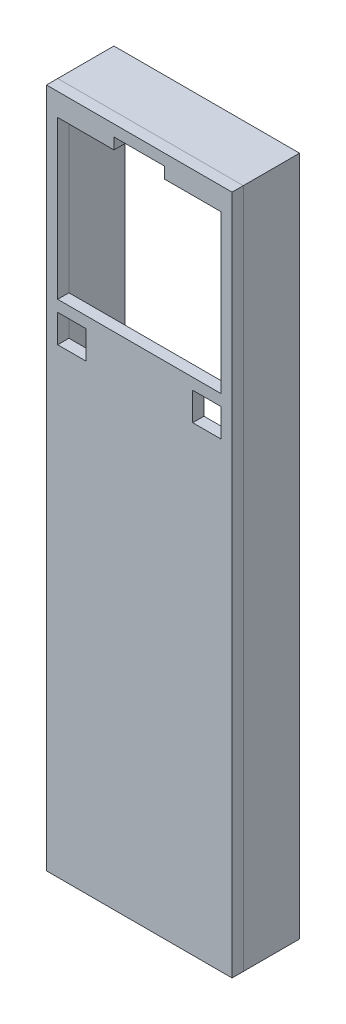
SolidWorks part; units mm, degrees
ref_plane "Plano frontal" through (0, 0, 0) normal (0, 0, 1) x (1, 0, 0)
ref_plane "Plano superior" through (0, 0, 0) normal (0, 1, 0) x (1, 0, 0)
ref_plane "Plano direito" through (0, 0, 0) normal (1, 0, 0) x (0, 0, -1)
sketch "Esboço1" plane through (0, 0, 0) normal (0, 0, 1) x (1, 0, 0)
  line L0 (0, 0) -> (0, 87)
  line L1 (0, 115) -> (29, 115)
  line L2 (29, 115) -> (29, 87)
  line L3 (29, 0) -> (0, 0)
  line L4 (0, 0) -> (0, 1.5)
  line L5 (0, 1.5) -> (1.5, 1.5)
  line L6 (14.5, 0) -> (14.5, 6.4035)
  line L7 (-2, -2) -> (-2, 119)
  line L8 (-2, 117) -> (31, 117)
  line L9 (31, 119) -> (31, -2)
  line L10 (31, -2) -> (-2, -2)
  line L11 (-2, 85) -> (24, 85)
  line L12 (0, 80) -> (5, 80)
  line L13 (0, 85) -> (5, 85)
  line L14 (5, 85) -> (5, 80)
  line L15 (0, 87) -> (24, 87)
  line L16 (24, 80) -> (24, 85)
  line L17 (24, 85) -> (31, 85)
  line L18 (24, 80) -> (29, 80)
  line L19 (0, 85) -> (29, 85) construction
  line L20 (24, 87) -> (29, 87)
  line L21 (0, 80) -> (29, 80) construction
  line L22 (0, 115) -> (10, 115)
  line L23 (10, 115) -> (10, 117)
  line L24 (29, 115) -> (19, 115)
  line L25 (19, 115) -> (19, 117)
  line L26 (-2, 119) -> (31, 119)
  line L27 (-2, -2) -> (-2, 117) construction
  line L28 (31, 117) -> (31, -2) construction
  line L29 (29, 87) -> (29, 0)
  line L30 (24, 87) -> (31, 87) construction
  line L31 (0, 87) -> (0, 115)
  line L32 (29, 115) -> (29, 0) construction
  line L34 (0, 0) -> (0, 115) construction
  line L35 (-2, 87) -> (24, 87) construction
  circle A0 centre (1.5, 1.5) radius 1.5
  circle A1 centre (27.5, 1.5) radius 1.5
  circle A2 centre (10, 82.5) radius 2
  circle A3 centre (19, 82.5) radius 2
  dimension "D1" = 2
  dimension "D4" = 2
  dimension "D5" = 2
  dimension "D2" = 30
  dimension "D3" = 5
extrude "Ressalto-extrusão1" add sketch "Esboço1" against normal blind 10 contours L26 L7 L8 L9 | L2 L29 L17 L9 L8 L25 L1 | L17 L29 L3 L0 L11 L7 L10 L9 | L0 L31 L1 L23 L8 L7 L11 region at (0.75, -0.9305, 0) region at (-1, 85.3418, 0) region at (14.5, 118, 0) region at (29.3418, 101, 0)
extrude "Ressalto-extrusão2" add sketch "Esboço1<4>" against normal blind 2.5 separate body contours A2 | A3 | A1 | A0 region at (1.5, 2.9576, 0) region at (27.5, 1.5, 0) region at (10, 82.5, 0) region at (19, 82.5, 0)
sketch "Esboço1<4>" plane through (0, 0, 0) normal (0, 0, 1) x (1, 0, 0) same geometry as "Esboço1"
sketch "Esboço2" plane through (0, 0, 0) normal (0, 0, 1) x (1, 0, 0)
  line L0 (0, 85) -> (5, 85)
  line L1 (-2, 119) -> (31, 119)
  line L2 (-2, 119) -> (-2, -2)
  line L3 (-2, -2) -> (31, -2)
  line L4 (31, 119) -> (31, -2)
  line L5 (5, 85) -> (5, 80)
  line L6 (5, 80) -> (0, 80)
  line L7 (0, 80) -> (0, 85)
  line L8 (24, 85) -> (24, 80)
  line L9 (24, 80) -> (29, 80)
  line L10 (29, 80) -> (29, 85)
  line L11 (29, 85) -> (24, 85)
  line L12 (0, 115) -> (10, 115)
  line L13 (10, 115) -> (10, 117)
  line L14 (10, 117) -> (19, 117)
  line L15 (19, 117) -> (19, 115)
  line L16 (19, 115) -> (29, 115)
  line L17 (29, 115) -> (29, 87)
  line L18 (29, 87) -> (0, 87)
  line L19 (0, 87) -> (0, 115)
extrude "Ressalto-extrusão8" add sketch "Esboço2" along normal blind 2 separate body
